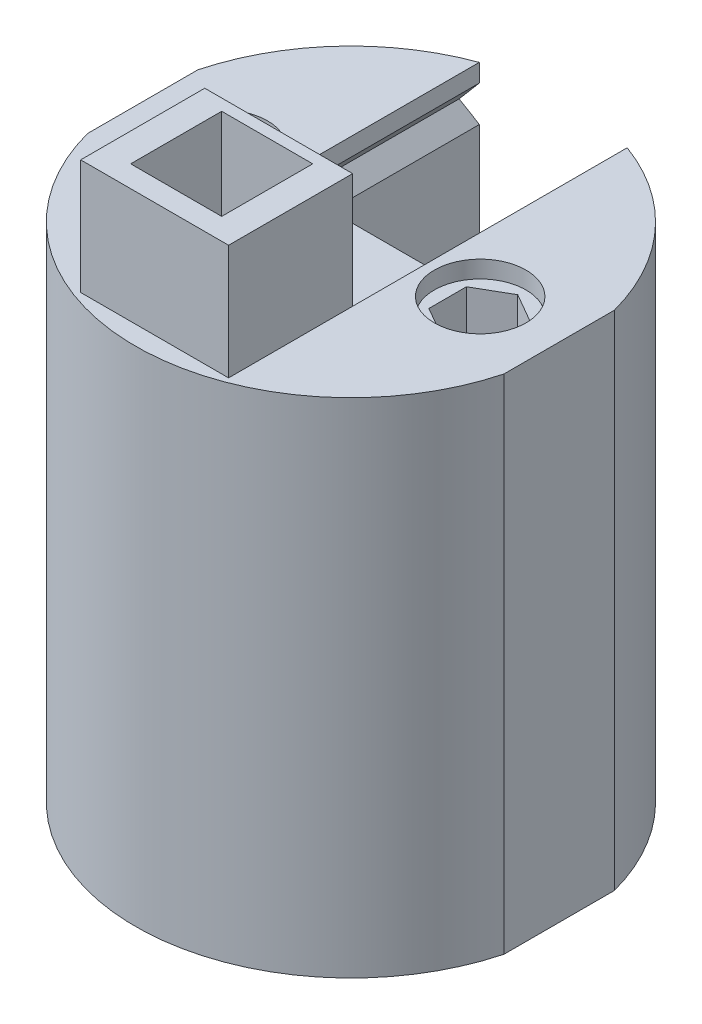
SolidWorks part; units mm, degrees
ref_plane "前视基准面" through (0, 0, 0) normal (0, 0, 1) x (1, 0, 0)
ref_plane "上视基准面" through (0, 0, 0) normal (0, 1, 0) x (1, 0, 0)
ref_plane "右视基准面" through (0, 0, 0) normal (1, 0, 0) x (0, 0, -1)
sketch "草图1" plane through (0, 0, 0) normal (0, 1, 0) x (1, 0, 0)
  circle A0 centre (0, 0) radius 15
  dimension "D1" = 30
extrude "凸台-拉伸1" add sketch "草图1" along normal blind 35
sketch "草图2" plane through (0, 35, 0) normal (0, 1, 0) x (1, 0, 0)
  line L0 (0, 0) -> (0, 9.4079) construction
  line L1 (0, 0) -> (9, 0) construction
  circle A0 centre (9, 0) radius 1.4
  circle A1 centre (-9, 0) radius 1.4
  dimension "D2" = 2.8
  dimension "D1" = 18
extrude "切除-拉伸1" cut sketch "草图2" against normal through all
sketch "草图4" plane through (0, 35, 0) normal (0, 1, 0) x (1, 0, 0)
  line L0 (0, 0) -> (0, -9) construction
  line L2 (-3.17, -12.17) -> (3.17, -12.17)
  line L3 (-3.17, -12.17) -> (-3.17, -5.83)
  line L4 (-3.17, -5.83) -> (3.17, -5.83)
  line L5 (3.17, -12.17) -> (3.17, -5.83)
  line L6 (-3.17, -12.17) -> (3.17, -5.83) construction
  line L7 (-3.17, -5.83) -> (3.17, -12.17) construction
  line L8 (-5.15, -13.67) -> (5.15, -13.67)
  line L9 (-5.15, -13.67) -> (-5.15, -5.03)
  line L10 (-5.15, -5.03) -> (5.15, -5.03)
  line L11 (5.15, -13.67) -> (5.15, -5.03)
  line L12 (-5.15, -13.67) -> (5.15, -5.03) construction
  line L13 (-5.15, -5.03) -> (5.15, -13.67) construction
  point P7 (0, -9.35)
  dimension "D1" = 6.34
  dimension "D2" = 6.34
  dimension "D3" = 0.8
  dimension "D5" = 1.5
  dimension "D6" = 9
  dimension "D7" = 10.3
extrude "凸台-拉伸2" add sketch "草图4" along normal blind 8
sketch "草图5" plane through (0, 35, 0) normal (0, 1, 0) x (1, 0, 0)
  line L0 (5.15, -5.03) -> (-5.15, -5.03) construction
  line L1 (5.15, -5.03) -> (-5.15, -5.03) construction
  line L3 (-5.15, -5.03) -> (5.15, -5.03)
  line L4 (-5.15, -5.03) -> (-5.15, 15)
  line L5 (-5.15, 15) -> (5.15, 15)
  line L6 (5.15, -5.03) -> (5.15, 15)
  circle A0 centre (0, 0) radius 15 construction
extrude "切除-拉伸2" cut sketch "草图5" against normal blind 5
sketch "草图6" plane through (0, 0, 5.03) normal (0, 0, -1) x (-1, 0, 0)
  line L0 (-5.15, 30) -> (-5.15, 35) construction
  line L1 (-5.15, 30) -> (-5.15, 35) construction
  line L2 (-5.15, 32.5) -> (-8.5283, 32.5) construction
  line L3 (-6.15, 32.5) -> (-5.15, 33.75)
  line L4 (-5.15, 33.75) -> (-5.15, 31.25)
  line L5 (-6.15, 32.5) -> (-5.15, 31.25)
  line L6 (0, 0) -> (0, 49.1632) construction
  line L7 (6.15, 32.5) -> (5.15, 33.75)
  line L8 (5.15, 33.75) -> (5.15, 31.25)
  line L9 (6.15, 32.5) -> (5.15, 31.25)
  dimension "D1" = 2.5
  dimension "D2" = 1
extrude "切除-拉伸3" cut sketch "草图6" along normal through all
sketch "草图7" plane through (0, 30, 0) normal (0, 1, 0) x (1, 0, 0)
  line L0 (-5.15, 4.97) -> (5.15, 4.97)
  line L3 (-5.15, 14.0882) -> (-5.15, -5.03)
  line L4 (-5.15, -5.03) -> (5.15, -5.03)
  line L5 (5.15, -5.03) -> (5.15, 14.0882)
  line L6 (-5.15, 14.0882) -> (-5.15, -5.03)
  line L7 (-5.15, -5.03) -> (5.15, -5.03)
  line L8 (5.15, -5.03) -> (5.15, 14.0882)
  arc A1 (5.15, 14.0882) -> (-5.15, 14.0882) centre (0, 0) ccw
  arc A2 (5.15, 14.0882) -> (-5.15, 14.0882) centre (0, 0) ccw
  arc M6 (5.15, 14.0882) -> (-5.15, 14.0882) centre (0, 0) ccw
  line M7 (-5.15, 14.0882) -> (-5.15, -5.03)
  line M9 (5.15, -5.03) -> (5.15, 14.0882)
  dimension "D2" = 10
  dimension "D1" = 0
extrude "切除-拉伸4" cut sketch "草图7" against normal through all contours L0 M7 M9 M6 region at (0, 30, -9.8387)
sketch "草图8" plane through (0, 35, 0) normal (0, 1, 0) x (1, 0, 0)
  line L0 (0, 0) -> (0, -12.17) construction
  line L1 (-3.17, -12.17) -> (3.17, -12.17) construction
  line L2 (3.17, -5.83) -> (-3.17, -5.83) construction
  line L3 (-1.15, -12.17) -> (1.15, -12.17)
  line L4 (-1.15, -12.17) -> (-1.15, -5.83)
  line L5 (-1.15, -5.83) -> (1.15, -5.83)
  line L6 (1.15, -12.17) -> (1.15, -5.83)
  line L7 (-1.15, -12.17) -> (1.15, -5.83) construction
  line L8 (-1.15, -5.83) -> (1.15, -12.17) construction
  point P5 (0, -9)
  dimension "D1" = 2.3
extrude "凸台-拉伸3" add sketch "草图8" along normal blind 1.6
sketch "草图9" plane through (0, 0, 0) normal (1, 0, 0) x (0, 0, -1)
  line L0 (-9, 36.6) -> (-9, 27.97)
  line L1 (-5.83, 36.6) -> (-12.17, 36.6) construction
  line L2 (-9, 27.97) -> (-3.03, 22)
  line L3 (-3.03, 22) -> (4.97, 22)
  line L4 (4.97, 0) -> (4.97, 30) construction
  line L5 (4.97, 30) -> (-5.03, 30) construction
  dimension "D1" = 135
  dimension "D2" = 135
  dimension "D3" = 8
  dimension "D4" = 8
sketch "草图10" plane through (0, 35, 0) normal (0, 1, 0) x (1, 0, 0)
  line L0 (-3.17, -9) -> (3.17, -9) construction
  line L1 (-3.17, -5.83) -> (-3.17, -12.17) construction
  line L2 (3.17, -12.17) -> (3.17, -5.83) construction
  line L3 (1.15, -12.17) -> (1.15, -5.83) construction
  line L4 (1.15, -10.5) -> (3.17, -10.5)
  line L5 (1.15, -10.5) -> (1.15, -7.5)
  line L6 (1.15, -7.5) -> (3.17, -7.5)
  line L7 (3.17, -10.5) -> (3.17, -7.5)
  line L8 (1.15, -10.5) -> (3.17, -7.5) construction
  line L9 (1.15, -7.5) -> (3.17, -10.5) construction
  line L10 (0, -9) -> (0, -14.2393) construction
  line L11 (-1.15, -10.5) -> (-1.15, -7.5)
  line L12 (-1.15, -7.5) -> (-3.17, -7.5)
  line L13 (-3.17, -10.5) -> (-3.17, -7.5)
  line L14 (-1.15, -10.5) -> (-3.17, -10.5)
  point P6 (2.16, -9)
  dimension "D1" = 3
sweep "切除-扫描1" cut profiles "草图10" path "草图9"
sketch "草图11" plane through (0, 0, 0) normal (0, -1, 0) x (1, 0, 0)
  line L0 (3.17, 5.83) -> (-3.17, 5.83) construction
  line L1 (-3.17, 5.83) -> (-3.17, 12.17) construction
  line L2 (3.17, 12.17) -> (3.17, 5.83) construction
  line L3 (-3.17, 12.17) -> (3.17, 12.17) construction
  line L4 (3.17, 5.83) -> (-3.17, 5.83)
  line L5 (-3.17, 5.83) -> (-3.17, 12.17)
  line L6 (3.17, 12.17) -> (3.17, 5.83)
  line L7 (-3.17, 12.17) -> (3.17, 12.17)
extrude "切除-拉伸5" cut sketch "草图11" against normal blind 6.5
sketch "草图12" plane through (0, 6.5, 0) normal (0, -1, 0) x (1, 0, 0)
  line L0 (-1.15, 7.5) -> (-3.17, 7.5) construction
  line L1 (-3.17, 10.5) -> (-1.15, 10.5) construction
  line L2 (-1.15, 7.5) -> (-3.17, 7.5) construction
  line L3 (-3.17, 10.5) -> (-1.15, 10.5) construction
  line L4 (0, 0) -> (0, 13.1236) construction
  line L5 (-1.15, 10.5) -> (-3.17, 10.5)
  line L6 (-1.15, 10.5) -> (-1.15, 7.5)
  line L7 (-1.15, 7.5) -> (-3.17, 7.5)
  line L8 (-3.17, 10.5) -> (-3.17, 7.5)
  line L9 (1.15, 10.5) -> (3.17, 10.5)
  line L10 (3.17, 10.5) -> (3.17, 7.5)
  line L11 (1.15, 7.5) -> (3.17, 7.5)
  line L12 (1.15, 10.5) -> (1.15, 7.5)
sketch "草图13" plane through (0, 0, 0) normal (1, 0, 0) x (0, 0, -1)
  line L0 (-12.17, 6.5) -> (-5.83, 6.5) construction
  line L1 (-12.17, 6.5) -> (-5.83, 6.5) construction
  line L2 (-9, 6.5) -> (-9, 13.5)
  line L3 (-9, 13.5) -> (-4.5, 18)
  line L4 (-4.5, 18) -> (4.97, 18)
  line L5 (4.97, 0) -> (4.97, 30) construction
  line L6 (4.97, 0) -> (4.97, 30) construction
  dimension "D1" = 7
  dimension "D2" = 135
  dimension "D3" = 12
sweep "切除-扫描2" cut profiles "草图12" path "草图13"
sketch "草图14" plane through (0, 0, 12.17) normal (0, 0, -1) x (-1, 0, 0)
  line L0 (0, 0) -> (0, 42.2897) construction
  line L1 (3.17, 35) -> (1.15, 35)
  line L2 (3.17, 35) -> (3.17, 36.6)
  line L3 (3.17, 36.6) -> (1.15, 36.6)
  line L4 (1.15, 35) -> (1.15, 36.6)
  line L5 (-1.15, 35) -> (-1.15, 36.6)
  line L6 (-3.17, 36.6) -> (-1.15, 36.6)
  line L7 (-3.17, 35) -> (-3.17, 36.6)
  line L8 (-3.17, 35) -> (-1.15, 35)
extrude "切除-拉伸6" [suppressed] cut sketch "草图14" against normal blind 6.5
sketch "草图15" plane through (0, 35, 0) normal (0, 1, 0) x (1, 0, 0)
  line L0 (9, 2.6154) -> (9, 0) construction
  line L1 (9, 2.6154) -> (6.735, 1.3077)
  line L2 (6.735, 1.3077) -> (6.735, -1.3077)
  line L3 (6.735, -1.3077) -> (9, -2.6154)
  line L4 (9, -2.6154) -> (11.265, -1.3077)
  line L5 (11.265, -1.3077) -> (11.265, 1.3077)
  line L6 (11.265, 1.3077) -> (9, 2.6154)
  line L7 (0, 0) -> (0, 5.3841) construction
  line L8 (-11.265, -1.3077) -> (-11.265, 1.3077)
  line L9 (-9, -2.6154) -> (-11.265, -1.3077)
  line L10 (-6.735, -1.3077) -> (-9, -2.6154)
  line L11 (-6.735, 1.3077) -> (-6.735, -1.3077)
  line L12 (-9, 2.6154) -> (-6.735, 1.3077)
  line L13 (-11.265, 1.3077) -> (-9, 2.6154)
  circle A0 centre (9, 0) radius 1.4 construction
  circle A1 centre (9, 0) radius 1.4 construction
  circle A2 centre (9, 0) radius 2.265 construction
  dimension "D1" = 4.53
extrude "切除-拉伸7" cut sketch "草图15" against normal blind 5
sketch "草图16" plane through (0, 35, 0) normal (0, 1, 0) x (1, 0, 0)
  line L0 (0, 0) -> (0, 7.5468) construction
  circle A0 centre (9, 0) radius 1.4 construction
  circle A1 centre (9, 0) radius 1.4 construction
  circle A2 centre (9, 0) radius 3.19
  circle A3 centre (-9, 0) radius 3.19
  dimension "D1" = 6.38
extrude "切除-拉伸8" cut sketch "草图16" against normal blind 1.2
ref_plane "基准面1" through (0, 17.5, 0) normal (0, 1, 0) x (1, 0, 0)
mirror "镜向1" about plane through (0, 17.5, 0) normal (0, 1, 0) of "切除-拉伸8", "切除-拉伸7"
sketch "草图17" plane through (0, 35, 0) normal (0, 1, 0) x (1, 0, 0)
  line L0 (14.5, 3.8406) -> (14.5, -3.8406)
  line L1 (0, 0) -> (15, 0) construction
  line L2 (0, 0) -> (0, 8.1062) construction
  line L3 (-14.5, 3.8406) -> (-14.5, -3.8406)
  arc A0 (-5.15, 14.0882) -> (5.15, 14.0882) centre (0, 0) ccw construction
  arc A1 (14.5, -3.8406) -> (14.5, 3.8406) centre (0, 0) ccw
  arc A2 (-14.5, -3.8406) -> (-14.5, 3.8406) centre (0, 0) cw
  dimension "D1" = 0.5
extrude "切除-拉伸9" cut sketch "草图17" against normal through all
sketch "草图18" plane through (-14.5, 0, 0) normal (-1, 0, 0) x (0, 0, 1)
  line L0 (0, 0) -> (0, 9.8297) construction
  circle A0 centre (0, 9.8297) radius 1.65
  dimension "D1" = 3.3
chamfer "倒角1" distance 1.1 angle 45 4 edges at (-3.17, 19.5, 0.0757) (-1.15, 19.5, 0.0757) (3.17, 19.5, 0.0757) (1.15, 19.5, 0.0757)
chamfer "倒角2" distance 1 angle 45 4 edges at (1.15, 23.5, -1.2807) (3.17, 23.5, -1.2807) (-1.15, 23.5, -1.2807) (-3.17, 23.5, -1.2807)
